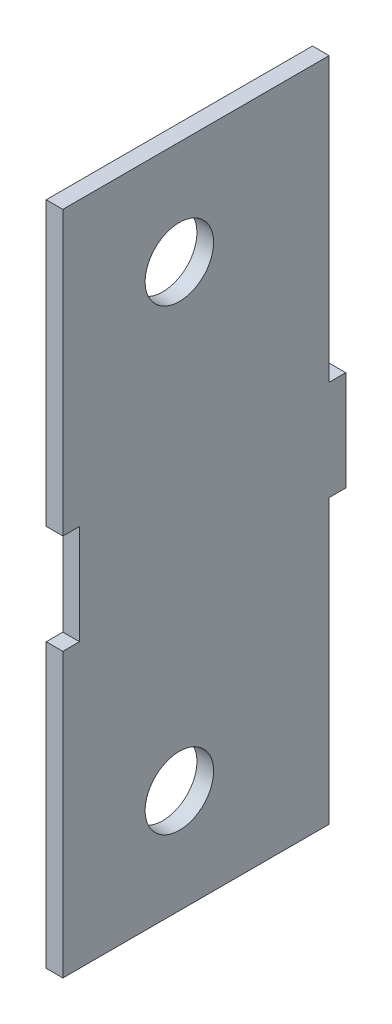
SolidWorks part; units mm, degrees
material "AISI 4130 Steel, annealed at 865C"
ref_plane "Front Plane" through (0, 0, 0) normal (0, 0, 1) x (1, 0, 0)
ref_plane "Top Plane" through (0, 0, 0) normal (0, 1, 0) x (1, 0, 0)
ref_plane "Right Plane" through (0, 0, 0) normal (1, 0, 0) x (0, 0, -1)
sketch "Sketch2" plane through (0, 0, 0) normal (1, 0, 0) x (0, 0, -1)
  line L0 (-1.5875, 21.844) -> (-1.5875, -21.844) construction
  line L1 (-12.7, -31.75) -> (12.7, -31.75)
  line L2 (-12.7, -31.75) -> (-12.7, 31.75)
  line L3 (-12.7, 31.75) -> (12.7, 31.75)
  line L4 (12.7, -31.75) -> (12.7, 31.75)
  line L5 (-12.7, -31.75) -> (12.7, 31.75) construction
  line L6 (-12.7, 31.75) -> (12.7, -31.75) construction
  line L7 (0, 0) -> (-1.5875, 0) construction
  circle A0 centre (-1.5875, 21.844) radius 3.2639
  circle A1 centre (-1.5875, -21.844) radius 3.2639
  point P0 (0, 0)
  point P6 (0, 0)
  point P13 (-1.5875, 0)
  dimension "D3" = 6.5278
  dimension "D4" = 6.5278
  dimension "D1" = 25.4
  dimension "D2" = 63.5
  dimension "D5" = 90
  dimension "D6" = 43.688
  dimension "D7" = 1.5875
extrude "Boss-Extrude1" add sketch "Sketch2" along normal blind 1.5875
sketch "Sketch3" plane through (1.5875, 0, 0) normal (1, 0, 0) x (0, 0, -1)
  line L0 (-12.7, 0) -> (12.7, 0) construction
  line L1 (-12.7, 31.75) -> (-12.7, -31.75) construction
  line L2 (12.7, -31.75) -> (12.7, 31.75) construction
  line L4 (-12.7, 4.7625) -> (-11.1125, 4.7625)
  line L5 (-12.7, 4.7625) -> (-12.7, -4.7625)
  line L6 (-12.7, -4.7625) -> (-11.1125, -4.7625)
  line L7 (-11.1125, 4.7625) -> (-11.1125, -4.7625)
  line L8 (12.7, 4.7625) -> (14.2875, 4.7625)
  line L9 (12.7, 4.7625) -> (12.7, -4.7625)
  line L10 (12.7, -4.7625) -> (14.2875, -4.7625)
  line L11 (14.2875, 4.7625) -> (14.2875, -4.7625)
  point P14 (-11.1125, 0)
  dimension "D1" = 9.525
  dimension "D2" = 1.5875
  dimension "D3" = 1.5875
extrude "Boss-Extrude2" add sketch "Sketch3" against normal blind 1.5875 contours L9 L8 L11 L10
extrude "Cut-Extrude1" cut sketch "Sketch3<4>" against normal blind 3.175 contours L7 L6 L5 L4
sketch "Sketch3<4>" plane through (1.5875, 0, 0) normal (1, 0, 0) x (0, 0, -1) same geometry as "Sketch3"
